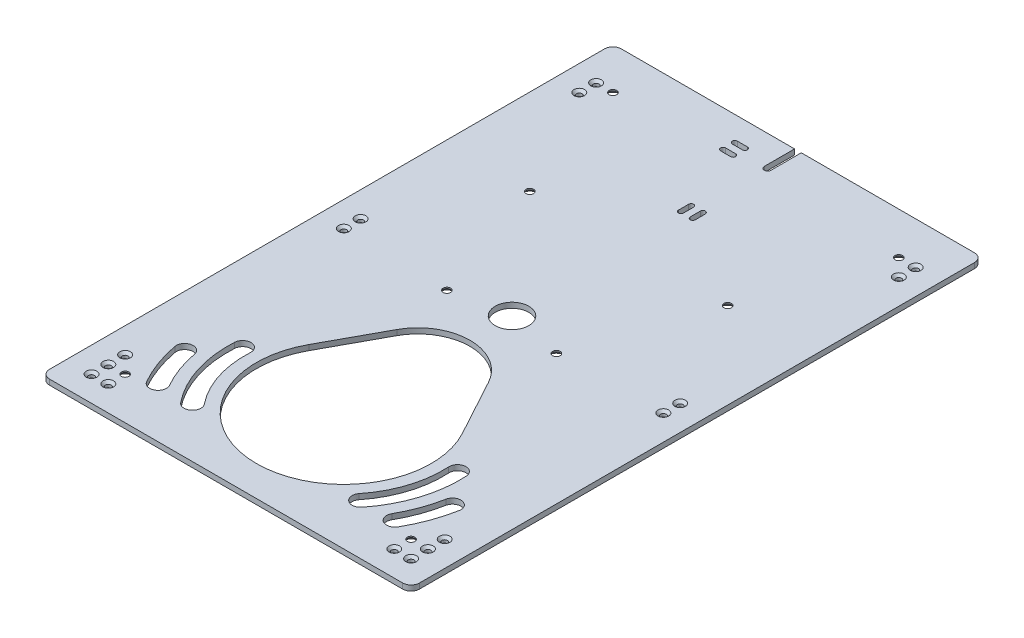
SolidWorks part; units mm, degrees
material "Acrylic (Medium-high impact)"
ref_plane "Front Plane" through (0, 0, 0) normal (0, 0, 1) x (1, 0, 0)
ref_plane "Top Plane" through (0, 0, 0) normal (0, 1, 0) x (1, 0, 0)
ref_plane "Right Plane" through (0, 0, 0) normal (1, 0, 0) x (0, 0, -1)
sketch "Sketch1" plane through (0, 0, 0) normal (0, 1, 0) x (1, 0, 0)
  line L0 (0, -170) -> (0, 170) construction
  line L1 (-110, 170) -> (110, 170)
  line L2 (-110, 170) -> (-110, -170)
  line L3 (-110, -170) -> (110, -170)
  line L4 (110, 170) -> (110, -170)
  line L5 (110, 0) -> (-110, 0) construction
  dimension "D1" = 340
  dimension "D2" = 220
extrude "Boss-Extrude1" add sketch "Sketch1" along normal blind 3.175
fillet "Fillet1" radius 5 4 edges at (110, 1.5875, -170) (-110, 1.5875, -170) (-110, 1.5875, 170) (110, 1.5875, 170)
sketch "Sketch2" plane through (0, 3.175, 0) normal (0, 1, 0) x (1, 0, 0)
  line L0 (-110, -160) -> (110, -160) construction
  line L1 (-27.1963, -41.1673) -> (-45.6812, -75.156)
  line L2 (-110, 165) -> (-110, -165) construction
  line L3 (110, -165) -> (110, 165) construction
  line L4 (-105, -170) -> (105, -170) construction
  line L5 (0, -160) -> (0, -100) construction
  line L6 (0, -100) -> (0, -25) construction
  line L7 (27.1963, -41.1673) -> (45.6812, -75.156)
  line L8 (-32, -50) -> (32, -50) construction
  line L9 (-110, 0) -> (110, 0) construction
  line L10 (0, 170) -> (0, 152) construction
  line L11 (105, 170) -> (-105, 170) construction
  line L12 (2, 170) -> (2, 152)
  line L13 (-2, 170) -> (-2, 152)
  line L14 (0, 152) -> (0, 111.4071) construction
  line L15 (-3.5, 110) -> (-3.5, 104) construction
  line L16 (-2, 110) -> (-2, 104)
  line L17 (-5, 110) -> (-5, 104)
  line L18 (3.5, 110) -> (3.5, 104) construction
  line L19 (2, 110) -> (2, 104)
  line L20 (5, 110) -> (5, 104)
  line L21 (0, 152) -> (-62.4405, 152) construction
  line L22 (-23, 155.5) -> (-17, 155.5) construction
  line L23 (-23, 157) -> (-17, 157)
  line L24 (-23, 154) -> (-17, 154)
  line L25 (-23, 148.5) -> (-17, 148.5) construction
  line L26 (-23, 147) -> (-17, 147)
  line L27 (-23, 150) -> (-17, 150)
  arc A0 (-45.6812, -75.156) -> (45.6812, -75.156) centre (0, -100) ccw
  arc A1 (27.1963, -41.1673) -> (-27.1963, -41.1673) centre (0, -55.9582) ccw
  circle A2 centre (0, 0) radius 10
  arc A3 (2, 170) -> (-2, 170) centre (0, 170) ccw
  arc A4 (-2, 152) -> (2, 152) centre (0, 152) ccw
  arc A5 (-2, 110) -> (-5, 110) centre (-3.5, 110) ccw
  arc A6 (-5, 104) -> (-2, 104) centre (-3.5, 104) ccw
  arc A7 (2, 110) -> (5, 110) centre (3.5, 110) cw
  arc A8 (5, 104) -> (2, 104) centre (3.5, 104) cw
  arc A9 (-23, 157) -> (-23, 154) centre (-23, 155.5) ccw
  arc A10 (-17, 154) -> (-17, 157) centre (-17, 155.5) ccw
  arc A11 (-23, 147) -> (-23, 150) centre (-23, 148.5) cw
  arc A12 (-17, 150) -> (-17, 147) centre (-17, 148.5) cw
  point P27 (0, 161)
  point P36 (-3.5, 107)
  point P43 (3.5, 107)
  point P51 (-20, 155.5)
  point P58 (-20, 148.5)
  dimension "D1" = 52
  dimension "D7" = 20
  dimension "D8" = 2
  dimension "D10" = 1.5
  dimension "D14" = 2
  dimension "D2" = 10
  dimension "D3" = 60
  dimension "D4" = 75
  dimension "D5" = 64
  dimension "D6" = 50
  dimension "D9" = 18
  dimension "D11" = 6
  dimension "D12" = 2
  dimension "D13" = 60
  dimension "D15" = 20
extrude "Cut-Extrude1" cut sketch "Sketch2" against normal through all
hole_wizard "CSK for M3 Flat Head Machine Screw1" positions "Sketch4" profile "Sketch3" countersink size "M3" standard "Ansi Metric" end condition through all
sketch "Sketch4" plane through (0, 3.175, 0) normal (0, 1, 0) x (-1, 0, 0)
  line L0 (95, 170) -> (95, -170) construction
  line L1 (105, 170) -> (-105, 170) construction
  line L3 (110, 155) -> (85, 155) construction
  line L4 (110, -165) -> (110, 165) construction
  line L6 (-105, -170) -> (-2, -170) construction
  point P0 (85, 155)
  point P1 (95, 155)
  point P3 (95, 145)
  point P5 (95, 135)
  point P7 (95, 5)
  point P58 (95, -5)
  point P60 (95, -135)
  point P62 (95, -145)
  dimension "D1" = 15
  dimension "D2" = 15
  dimension "D3" = 10
  dimension "D4" = 20
  dimension "D5" = 10
  dimension "D6" = 150
  dimension "D7" = 10
  dimension "D8" = 130
  dimension "D9" = 10
sketch "Sketch3" plane through (-85, 3.175, 155) normal (1, 0, 0) x (0, 0, 1)
  line L0 (0, 0) -> (0, 3.175)
  line L1 (0, 3.175) -> (1.7, 3.175)
  line L2 (1.7, 3.175) -> (1.7, 1.45)
  line L3 (1.7, 1.45) -> (3.15, 0)
  line L5 (3.15, 0) -> (0, 0)
  line L6 (-1.7, 1.45) -> (-3.15, 0) construction
  line L11 (0, -6.35) -> (0, 107.95) construction
  dimension "Thru Hole Dia." = 3.4
  dimension "Thru Hole Depth" = 3.175
  dimension "Near C'Sink Dia." = 6.3
  dimension "Near C'Sink Angle" = 90
mirror "Mirror3" about plane through (0, 0, 0) normal (1, 0, 0) of "CSK for M3 Flat Head Machine Screw1"
hole_wizard "CSK for M4 Flat Head Machine Screw1" positions "Sketch6" profile "Sketch5" countersink size "M4" standard "Ansi Metric" end condition through all
sketch "Sketch6" plane through (0, 0, 0) normal (0, -1, 0) x (1, 0, 0)
  line L4 (0, 100) -> (85, 145) construction
  line L5 (0, 100) -> (85, -145) construction
  line L7 (-105, 170) -> (105, 170) construction
  line L8 (110, 165) -> (110, -165) construction
  line L9 (105, -170) -> (2, -170) construction
  arc A0 (45.6812, 75.156) -> (-45.6812, 75.156) centre (0, 100) ccw construction
  arc A1 (45.6812, 75.156) -> (-45.6812, 75.156) centre (0, 100) ccw construction
  point P1 (85, 145)
  point P3 (85, -145)
  point P5 (32.5564, 6.1611)
  point P7 (58.7782, -69.4195)
  dimension "D1" = 80
  dimension "D2" = 80
  dimension "D3" = 25
  dimension "D4" = 25
  dimension "D5" = 25
  dimension "D6" = 25
sketch "Sketch5" plane through (85, 0, 145) normal (1, 0, 0) x (0, 0, -1)
  line L0 (0, 0) -> (0, 3.175)
  line L1 (0, 3.175) -> (2.25, 3.175)
  line L2 (2.25, 3.175) -> (2.25, 2.45)
  line L3 (2.25, 2.45) -> (4.7, 0)
  line L5 (4.7, 0) -> (0, 0)
  line L6 (-2.25, 2.45) -> (-4.7, 0) construction
  line L11 (0, -6.35) -> (0, 107.95) construction
  dimension "Thru Hole Dia." = 4.5
  dimension "Thru Hole Depth" = 3.175
  dimension "Near C'Sink Dia." = 9.4
  dimension "Near C'Sink Angle" = 90
mirror "Mirror4" about plane through (0, 0, 0) normal (1, 0, 0) of "CSK for M4 Flat Head Machine Screw1"
sketch "Sketch7" plane through (0, 3.175, 0) normal (0, 1, 0) x (1, 0, 0)
  line L0 (-105, -170) -> (105, -170) construction
  line L2 (70.4344, -140) -> (49.96, -140) construction
  line L3 (79.599, -115) -> (63.8919, -96.281) construction
  line L4 (110, -165) -> (110, 165) construction
  arc A0 (-45.6812, -75.156) -> (45.6812, -75.156) centre (0, -100) ccw construction
  arc A1 (-45.6812, -75.156) -> (45.6812, -75.156) centre (0, -100) ccw construction
  arc A2 (53.8631, -143.125) -> (68.8834, -95.9904) centre (0, -100) ccw
  arc A3 (74.6855, -114.0741) -> (66.0866, -137.5309) centre (0, -100) cw
  arc A4 (74.7822, -142.4691) -> (84.5125, -115.9259) centre (0, -100) ccw
  arc A5 (58.9003, -96.5715) -> (46.0569, -136.875) centre (0, -100) cw
  arc A6 (46.0569, -136.875) -> (53.8631, -143.125) centre (49.96, -140) ccw
  arc A7 (68.8834, -95.9904) -> (58.9003, -96.5715) centre (63.8919, -96.281) ccw
  arc A8 (84.5125, -115.9259) -> (74.6855, -114.0741) centre (79.599, -115) ccw
  arc A9 (66.0866, -137.5309) -> (74.7822, -142.4691) centre (70.4344, -140) ccw
  dimension "D1" = 30
  dimension "D2" = 5
  dimension "D3" = 7
  dimension "D4" = 7
  dimension "D5" = 40
  dimension "D6" = 55
extrude "Cut-Extrude2" cut sketch "Sketch7" against normal through all
mirror "Mirror5" about plane through (0, 0, 0) normal (1, 0, 0) of "Cut-Extrude2"
